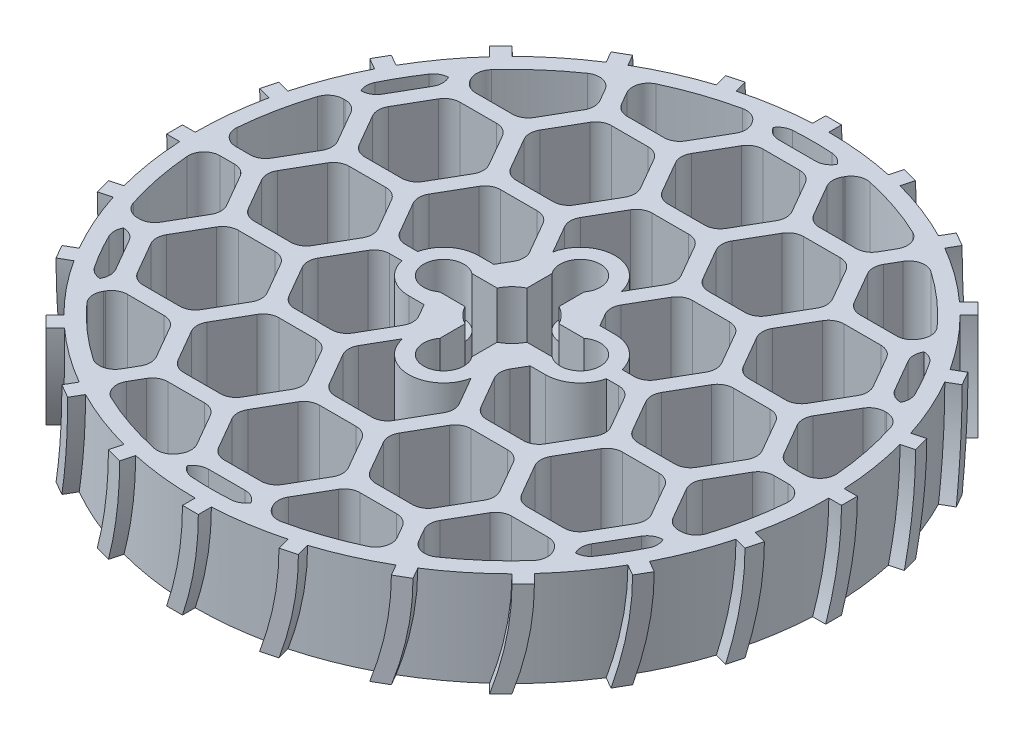
SolidWorks part; units mm, degrees
ref_plane "Front Plane" through (0, 0, 0) normal (0, 0, 1) x (1, 0, 0)
ref_plane "Top Plane" through (0, 0, 0) normal (0, 1, 0) x (1, 0, 0)
ref_plane "Right Plane" through (0, 0, 0) normal (1, 0, 0) x (0, 0, -1)
sketch "Sketch2" plane through (0, 0, 0) normal (0, 1, 0) x (1, 0, 0)
  line L0 (-17.7275, -5.0583) -> (-9.768, -5.0583)
  line L1 (-17.7275, 5.0583) -> (-9.768, 5.0583)
  line L2 (-21.548, 11) -> (-11, 11)
  line L3 (-21.548, -11) -> (-11, -11)
  line L4 (-21.548, 0) -> (0, 0) construction
  line L5 (11, 21.548) -> (11, 11)
  line L6 (-11, 21.548) -> (-11, 11)
  line L7 (5.0583, 17.7275) -> (5.0583, 9.768)
  line L8 (-5.0583, 17.7275) -> (-5.0583, 9.768)
  line L9 (21.548, -11) -> (11, -11)
  line L10 (21.548, 11) -> (11, 11)
  line L11 (17.7275, -5.0583) -> (9.768, -5.0583)
  line L12 (17.7275, 5.0583) -> (9.768, 5.0583)
  line L13 (-11, -21.548) -> (-11, -11)
  line L14 (11, -21.548) -> (11, -11)
  line L15 (-5.0583, -17.7275) -> (-5.0583, -9.768)
  line L16 (5.0583, -17.7275) -> (5.0583, -9.768)
  line L17 (0, 0) -> (-12.9904, 7.5) construction
  line L18 (-15.8771, -2.5) -> (-10.1036, -12.5)
  line L19 (-5.7735, -15) -> (5.7735, -15)
  line L20 (10.1036, -12.5) -> (15.8771, -2.5)
  line L21 (15.8771, 2.5) -> (10.1036, 12.5)
  line L22 (5.7735, 15) -> (-5.7735, 15)
  line L23 (-10.1036, 12.5) -> (-15.8771, 2.5)
  arc A0 (-21.548, 11) -> (-21.548, -11) centre (-21.548, 0) ccw
  arc A1 (-5.0583, 9.768) -> (-9.768, 5.0583) centre (0, 0) ccw
  circle A2 centre (-21.548, 0) radius 3.302
  circle A3 centre (-21.548, 0) radius 6.339
  arc A4 (-5.0583, 9.768) -> (-9.768, 5.0583) centre (0, 0) ccw
  arc A5 (11, 21.548) -> (-11, 21.548) centre (0, 21.548) ccw
  circle A6 centre (0, 21.548) radius 6.339
  circle A7 centre (0, 21.548) radius 3.302
  arc A8 (21.548, -11) -> (21.548, 11) centre (21.548, 0) ccw
  circle A9 centre (21.548, 0) radius 6.339
  circle A10 centre (21.548, 0) radius 3.302
  arc A11 (-11, -21.548) -> (11, -21.548) centre (0, -21.548) ccw
  circle A12 centre (0, -21.548) radius 6.339
  circle A13 centre (0, -21.548) radius 3.302
  arc A14 (9.768, 5.0583) -> (5.0583, 9.768) centre (0, 0) ccw
  arc A15 (5.0583, -9.768) -> (9.768, -5.0583) centre (0, 0) ccw
  arc A16 (-9.768, -5.0583) -> (-5.0583, -9.768) centre (0, 0) ccw
  circle A17 centre (0, 0) radius 100
  circle A18 centre (0, 0) radius 15 construction
  arc A19 (10.1036, 12.5) -> (5.7735, 15) centre (5.7735, 10) ccw
  arc A20 (15.8771, -2.5) -> (15.8771, 2.5) centre (11.547, 0) ccw
  arc A21 (10.1036, -12.5) -> (5.7735, -15) centre (5.7735, -10) cw
  arc A22 (-10.1036, -12.5) -> (-5.7735, -15) centre (-5.7735, -10) ccw
  arc A23 (-15.8771, -2.5) -> (-15.8771, 2.5) centre (-11.547, 0) cw
  arc A24 (-10.1036, 12.5) -> (-5.7735, 15) centre (-5.7735, 10) cw
  point P59 (0, 0)
  dimension "D1" = 6.604
  dimension "D2" = 12.678
  dimension "D3" = 11
  dimension "D8" = 22
  dimension "D10" = 200
  dimension "D12" = 5
  dimension "D4" = 21.548
  dimension "D5" = 7.9595
  dimension "D6" = 10.548
  dimension "D7" = 10.548
  dimension "D11" = 30
  dimension "D13" = 30
  dimension "D9" = 4
sketch "Sketch3" plane through (0, 0, 0) normal (0, 1, 0) x (1, 0, 0)
  line L0 (0, 0) -> (16.547, 0) construction
  line L1 (5.7735, 15) -> (-5.7735, 15)
  line L2 (-10.1036, 12.5) -> (-15.8771, 2.5)
  line L3 (-15.8771, -2.5) -> (-10.1036, -12.5)
  line L4 (-5.7735, -15) -> (5.7735, -15)
  line L5 (10.1036, -12.5) -> (15.8771, -2.5)
  line L6 (15.8771, 2.5) -> (10.1036, 12.5)
  line L7 (36.0844, 32.5) -> (24.5374, 32.5)
  line L8 (20.2073, 30) -> (14.4338, 20)
  line L9 (14.4338, 15) -> (20.2073, 5)
  line L10 (24.5374, 2.5) -> (36.0844, 2.5)
  line L11 (40.4145, 5) -> (46.188, 15)
  line L12 (46.188, 20) -> (40.4145, 30)
  line L13 (66.3953, 50) -> (54.8483, 50)
  line L14 (50.5181, 47.5) -> (44.7446, 37.5)
  line L15 (44.7446, 32.5) -> (50.5181, 22.5)
  line L16 (54.8483, 20) -> (66.3953, 20)
  line L17 (70.7254, 22.5) -> (76.4989, 32.5)
  line L18 (76.4989, 37.5) -> (70.7254, 47.5)
  line L19 (96.7062, 67.5) -> (85.1592, 67.5)
  line L20 (80.829, 65) -> (75.0555, 55)
  line L21 (75.0555, 50) -> (80.829, 40)
  line L22 (85.1592, 37.5) -> (96.7062, 37.5)
  line L23 (101.0363, 40) -> (106.8098, 50)
  line L24 (106.8098, 55) -> (101.0363, 65)
  line L25 (36.0844, 67.5) -> (24.5374, 67.5)
  line L26 (20.2073, 65) -> (14.4338, 55)
  line L27 (14.4338, 50) -> (20.2073, 40)
  line L28 (24.5374, 37.5) -> (36.0844, 37.5)
  line L29 (40.4145, 40) -> (46.188, 50)
  line L30 (46.188, 55) -> (40.4145, 65)
  line L31 (66.3953, 85) -> (54.8483, 85)
  line L32 (50.5181, 82.5) -> (44.7446, 72.5)
  line L33 (44.7446, 67.5) -> (50.5181, 57.5)
  line L34 (54.8483, 55) -> (66.3953, 55)
  line L35 (70.7254, 57.5) -> (76.4989, 67.5)
  line L36 (76.4989, 72.5) -> (70.7254, 82.5)
  line L37 (96.7062, 102.5) -> (85.1592, 102.5) [skipped]
  line L38 (80.829, 100) -> (75.0555, 90) [skipped]
  line L39 (75.0555, 85) -> (80.829, 75) [skipped]
  line L40 (85.1592, 72.5) -> (96.7062, 72.5) [skipped]
  line L41 (101.0363, 75) -> (106.8098, 85) [skipped]
  line L42 (106.8098, 90) -> (101.0363, 100) [skipped]
  line L43 (36.0844, 102.5) -> (24.5374, 102.5)
  line L44 (20.2073, 100) -> (14.4338, 90)
  line L45 (14.4338, 85) -> (20.2073, 75)
  line L46 (24.5374, 72.5) -> (36.0844, 72.5)
  line L47 (40.4145, 75) -> (46.188, 85)
  line L48 (46.188, 90) -> (40.4145, 100)
  line L49 (66.3953, 120) -> (54.8483, 120) [skipped]
  line L50 (50.5181, 117.5) -> (44.7446, 107.5) [skipped]
  line L51 (44.7446, 102.5) -> (50.5181, 92.5) [skipped]
  line L52 (54.8483, 90) -> (66.3953, 90) [skipped]
  line L53 (70.7254, 92.5) -> (76.4989, 102.5) [skipped]
  line L54 (76.4989, 107.5) -> (70.7254, 117.5) [skipped]
  line L55 (96.7062, 137.5) -> (85.1592, 137.5) [skipped]
  line L56 (80.829, 135) -> (75.0555, 125) [skipped]
  line L57 (75.0555, 120) -> (80.829, 110) [skipped]
  line L58 (85.1592, 107.5) -> (96.7062, 107.5) [skipped]
  line L59 (101.0363, 110) -> (106.8098, 120) [skipped]
  line L60 (106.8098, 125) -> (101.0363, 135) [skipped]
  line L61 (36.0844, 137.5) -> (24.5374, 137.5) [skipped]
  line L62 (20.2073, 135) -> (14.4338, 125) [skipped]
  line L63 (14.4338, 120) -> (20.2073, 110) [skipped]
  line L64 (24.5374, 107.5) -> (36.0844, 107.5) [skipped]
  line L65 (40.4145, 110) -> (46.188, 120) [skipped]
  line L66 (46.188, 125) -> (40.4145, 135) [skipped]
  line L67 (66.3953, 155) -> (54.8483, 155) [skipped]
  line L68 (50.5181, 152.5) -> (44.7446, 142.5) [skipped]
  line L69 (44.7446, 137.5) -> (50.5181, 127.5) [skipped]
  line L70 (54.8483, 125) -> (66.3953, 125) [skipped]
  line L71 (70.7254, 127.5) -> (76.4989, 137.5) [skipped]
  line L72 (76.4989, 142.5) -> (70.7254, 152.5) [skipped]
  line L73 (96.7062, 172.5) -> (85.1592, 172.5) [skipped]
  line L74 (80.829, 170) -> (75.0555, 160) [skipped]
  line L75 (75.0555, 155) -> (80.829, 145) [skipped]
  line L76 (85.1592, 142.5) -> (96.7062, 142.5) [skipped]
  line L77 (101.0363, 145) -> (106.8098, 155) [skipped]
  line L78 (106.8098, 160) -> (101.0363, 170) [skipped]
  line L79 (5.7735, 50) -> (-5.7735, 50) [skipped]
  line L80 (-10.1036, 47.5) -> (-15.8771, 37.5) [skipped]
  line L81 (-15.8771, 32.5) -> (-10.1036, 22.5) [skipped]
  line L82 (-5.7735, 20) -> (5.7735, 20) [skipped]
  line L83 (10.1036, 22.5) -> (15.8771, 32.5) [skipped]
  line L84 (15.8771, 37.5) -> (10.1036, 47.5) [skipped]
  line L85 (5.7735, 85) -> (-5.7735, 85) [skipped]
  line L86 (-10.1036, 82.5) -> (-15.8771, 72.5) [skipped]
  line L87 (-15.8771, 67.5) -> (-10.1036, 57.5) [skipped]
  line L88 (-5.7735, 55) -> (5.7735, 55) [skipped]
  line L89 (10.1036, 57.5) -> (15.8771, 67.5) [skipped]
  line L90 (15.8771, 72.5) -> (10.1036, 82.5) [skipped]
  line L91 (5.7735, 120) -> (-5.7735, 120) [skipped]
  line L92 (-10.1036, 117.5) -> (-15.8771, 107.5) [skipped]
  line L93 (-15.8771, 102.5) -> (-10.1036, 92.5) [skipped]
  line L94 (-5.7735, 90) -> (5.7735, 90) [skipped]
  line L95 (10.1036, 92.5) -> (15.8771, 102.5) [skipped]
  line L96 (15.8771, 107.5) -> (10.1036, 117.5) [skipped]
  line L97 (0, 0) -> (77.9423, 45) construction
  line L98 (106.8098, 20) -> (101.0363, 30)
  line L99 (96.7062, 32.5) -> (85.1592, 32.5)
  line L100 (80.829, 30) -> (75.0555, 20)
  line L101 (75.0555, 15) -> (80.829, 5)
  line L102 (85.1592, 2.5) -> (96.7062, 2.5)
  line L103 (101.0363, 5) -> (106.8098, 15)
  line L104 (106.8098, -15) -> (101.0363, -5)
  line L105 (96.7062, -2.5) -> (85.1592, -2.5)
  line L106 (80.829, -5) -> (75.0555, -15)
  line L107 (75.0555, -20) -> (80.829, -30)
  line L108 (85.1592, -32.5) -> (96.7062, -32.5)
  line L109 (101.0363, -30) -> (106.8098, -20)
  line L110 (106.8098, -50) -> (101.0363, -40)
  line L111 (96.7062, -37.5) -> (85.1592, -37.5)
  line L112 (80.829, -40) -> (75.0555, -50)
  line L113 (75.0555, -55) -> (80.829, -65)
  line L114 (85.1592, -67.5) -> (96.7062, -67.5)
  line L115 (101.0363, -65) -> (106.8098, -55)
  line L116 (76.4989, -32.5) -> (70.7254, -22.5)
  line L117 (66.3953, -20) -> (54.8483, -20)
  line L118 (50.5181, -22.5) -> (44.7446, -32.5)
  line L119 (44.7446, -37.5) -> (50.5181, -47.5)
  line L120 (54.8483, -50) -> (66.3953, -50)
  line L121 (70.7254, -47.5) -> (76.4989, -37.5)
  line L122 (76.4989, 2.5) -> (70.7254, 12.5)
  line L123 (66.3953, 15) -> (54.8483, 15)
  line L124 (50.5181, 12.5) -> (44.7446, 2.5)
  line L125 (44.7446, -2.5) -> (50.5181, -12.5)
  line L126 (54.8483, -15) -> (66.3953, -15)
  line L127 (70.7254, -12.5) -> (76.4989, -2.5)
  line L128 (46.188, -15) -> (40.4145, -5)
  line L129 (36.0844, -2.5) -> (24.5374, -2.5)
  line L130 (20.2073, -5) -> (14.4338, -15)
  line L131 (14.4338, -20) -> (20.2073, -30)
  line L132 (24.5374, -32.5) -> (36.0844, -32.5)
  line L133 (40.4145, -30) -> (46.188, -20)
  line L134 (70.7254, -82.5) -> (76.4989, -72.5)
  line L135 (76.4989, -67.5) -> (70.7254, -57.5)
  line L136 (66.3953, -55) -> (54.8483, -55)
  line L137 (50.5181, -57.5) -> (44.7446, -67.5)
  line L138 (44.7446, -72.5) -> (50.5181, -82.5)
  line L139 (54.8483, -85) -> (66.3953, -85)
  line L140 (40.4145, -100) -> (46.188, -90)
  line L141 (46.188, -85) -> (40.4145, -75)
  line L142 (36.0844, -72.5) -> (24.5374, -72.5)
  line L143 (20.2073, -75) -> (14.4338, -85)
  line L144 (14.4338, -90) -> (20.2073, -100)
  line L145 (24.5374, -102.5) -> (36.0844, -102.5)
  line L146 (10.1036, -117.5) -> (15.8771, -107.5)
  line L147 (15.8771, -102.5) -> (10.1036, -92.5)
  line L148 (5.7735, -90) -> (-5.7735, -90)
  line L149 (-10.1036, -92.5) -> (-15.8771, -102.5)
  line L150 (-15.8771, -107.5) -> (-10.1036, -117.5)
  line L151 (-5.7735, -120) -> (5.7735, -120)
  line L152 (10.1036, -82.5) -> (15.8771, -72.5)
  line L153 (15.8771, -67.5) -> (10.1036, -57.5)
  line L154 (5.7735, -55) -> (-5.7735, -55)
  line L155 (-10.1036, -57.5) -> (-15.8771, -67.5)
  line L156 (-15.8771, -72.5) -> (-10.1036, -82.5)
  line L157 (-5.7735, -85) -> (5.7735, -85)
  line L158 (40.4145, -65) -> (46.188, -55)
  line L159 (46.188, -50) -> (40.4145, -40)
  line L160 (36.0844, -37.5) -> (24.5374, -37.5)
  line L161 (20.2073, -40) -> (14.4338, -50)
  line L162 (14.4338, -55) -> (20.2073, -65)
  line L163 (24.5374, -67.5) -> (36.0844, -67.5)
  line L164 (10.1036, -47.5) -> (15.8771, -37.5)
  line L165 (15.8771, -32.5) -> (10.1036, -22.5)
  line L166 (5.7735, -20) -> (-5.7735, -20)
  line L167 (-10.1036, -22.5) -> (-15.8771, -32.5)
  line L168 (-15.8771, -37.5) -> (-10.1036, -47.5)
  line L169 (-5.7735, -50) -> (5.7735, -50)
  line L170 (-36.0844, -102.5) -> (-24.5374, -102.5)
  line L171 (-20.2073, -100) -> (-14.4338, -90)
  line L172 (-14.4338, -85) -> (-20.2073, -75)
  line L173 (-24.5374, -72.5) -> (-36.0844, -72.5)
  line L174 (-40.4145, -75) -> (-46.188, -85)
  line L175 (-46.188, -90) -> (-40.4145, -100)
  line L176 (-66.3953, -85) -> (-54.8483, -85)
  line L177 (-50.5181, -82.5) -> (-44.7446, -72.5)
  line L178 (-44.7446, -67.5) -> (-50.5181, -57.5)
  line L179 (-54.8483, -55) -> (-66.3953, -55)
  line L180 (-70.7254, -57.5) -> (-76.4989, -67.5)
  line L181 (-76.4989, -72.5) -> (-70.7254, -82.5)
  line L182 (-96.7062, -67.5) -> (-85.1592, -67.5)
  line L183 (-80.829, -65) -> (-75.0555, -55)
  line L184 (-75.0555, -50) -> (-80.829, -40)
  line L185 (-85.1592, -37.5) -> (-96.7062, -37.5)
  line L186 (-101.0363, -40) -> (-106.8098, -50)
  line L187 (-106.8098, -55) -> (-101.0363, -65)
  line L188 (-66.3953, -50) -> (-54.8483, -50)
  line L189 (-50.5181, -47.5) -> (-44.7446, -37.5)
  line L190 (-44.7446, -32.5) -> (-50.5181, -22.5)
  line L191 (-54.8483, -20) -> (-66.3953, -20)
  line L192 (-70.7254, -22.5) -> (-76.4989, -32.5)
  line L193 (-76.4989, -37.5) -> (-70.7254, -47.5)
  line L194 (-36.0844, -67.5) -> (-24.5374, -67.5)
  line L195 (-20.2073, -65) -> (-14.4338, -55)
  line L196 (-14.4338, -50) -> (-20.2073, -40)
  line L197 (-24.5374, -37.5) -> (-36.0844, -37.5)
  line L198 (-40.4145, -40) -> (-46.188, -50)
  line L199 (-46.188, -55) -> (-40.4145, -65)
  line L200 (-36.0844, -32.5) -> (-24.5374, -32.5)
  line L201 (-20.2073, -30) -> (-14.4338, -20)
  line L202 (-14.4338, -15) -> (-20.2073, -5)
  line L203 (-24.5374, -2.5) -> (-36.0844, -2.5)
  line L204 (-40.4145, -5) -> (-46.188, -15)
  line L205 (-46.188, -20) -> (-40.4145, -30)
  line L206 (-106.8098, -20) -> (-101.0363, -30)
  line L207 (-96.7062, -32.5) -> (-85.1592, -32.5)
  line L208 (-80.829, -30) -> (-75.0555, -20)
  line L209 (-75.0555, -15) -> (-80.829, -5)
  line L210 (-85.1592, -2.5) -> (-96.7062, -2.5)
  line L211 (-101.0363, -5) -> (-106.8098, -15)
  line L212 (-106.8098, 15) -> (-101.0363, 5)
  line L213 (-96.7062, 2.5) -> (-85.1592, 2.5)
  line L214 (-80.829, 5) -> (-75.0555, 15)
  line L215 (-75.0555, 20) -> (-80.829, 30)
  line L216 (-85.1592, 32.5) -> (-96.7062, 32.5)
  line L217 (-101.0363, 30) -> (-106.8098, 20)
  line L218 (-106.8098, 50) -> (-101.0363, 40)
  line L219 (-96.7062, 37.5) -> (-85.1592, 37.5)
  line L220 (-80.829, 40) -> (-75.0555, 50)
  line L221 (-75.0555, 55) -> (-80.829, 65)
  line L222 (-85.1592, 67.5) -> (-96.7062, 67.5)
  line L223 (-101.0363, 65) -> (-106.8098, 55)
  line L224 (-76.4989, 32.5) -> (-70.7254, 22.5)
  line L225 (-66.3953, 20) -> (-54.8483, 20)
  line L226 (-50.5181, 22.5) -> (-44.7446, 32.5)
  line L227 (-44.7446, 37.5) -> (-50.5181, 47.5)
  line L228 (-54.8483, 50) -> (-66.3953, 50)
  line L229 (-70.7254, 47.5) -> (-76.4989, 37.5)
  line L230 (-76.4989, -2.5) -> (-70.7254, -12.5)
  line L231 (-66.3953, -15) -> (-54.8483, -15)
  line L232 (-50.5181, -12.5) -> (-44.7446, -2.5)
  line L233 (-44.7446, 2.5) -> (-50.5181, 12.5)
  line L234 (-54.8483, 15) -> (-66.3953, 15)
  line L235 (-70.7254, 12.5) -> (-76.4989, 2.5)
  line L236 (-46.188, 15) -> (-40.4145, 5)
  line L237 (-36.0844, 2.5) -> (-24.5374, 2.5)
  line L238 (-20.2073, 5) -> (-14.4338, 15)
  line L239 (-14.4338, 20) -> (-20.2073, 30)
  line L240 (-24.5374, 32.5) -> (-36.0844, 32.5)
  line L241 (-40.4145, 30) -> (-46.188, 20)
  line L242 (-70.7254, 82.5) -> (-76.4989, 72.5)
  line L243 (-76.4989, 67.5) -> (-70.7254, 57.5)
  line L244 (-66.3953, 55) -> (-54.8483, 55)
  line L245 (-50.5181, 57.5) -> (-44.7446, 67.5)
  line L246 (-44.7446, 72.5) -> (-50.5181, 82.5)
  line L247 (-54.8483, 85) -> (-66.3953, 85)
  line L248 (-40.4145, 100) -> (-46.188, 90)
  line L249 (-46.188, 85) -> (-40.4145, 75)
  line L250 (-36.0844, 72.5) -> (-24.5374, 72.5)
  line L251 (-20.2073, 75) -> (-14.4338, 85)
  line L252 (-14.4338, 90) -> (-20.2073, 100)
  line L253 (-24.5374, 102.5) -> (-36.0844, 102.5)
  line L254 (-10.1036, 117.5) -> (-15.8771, 107.5)
  line L255 (-15.8771, 102.5) -> (-10.1036, 92.5)
  line L256 (-5.7735, 90) -> (5.7735, 90)
  line L257 (10.1036, 92.5) -> (15.8771, 102.5)
  line L258 (15.8771, 107.5) -> (10.1036, 117.5)
  line L259 (5.7735, 120) -> (-5.7735, 120)
  line L260 (-10.1036, 82.5) -> (-15.8771, 72.5)
  line L261 (-15.8771, 67.5) -> (-10.1036, 57.5)
  line L262 (-5.7735, 55) -> (5.7735, 55)
  line L263 (10.1036, 57.5) -> (15.8771, 67.5)
  line L264 (15.8771, 72.5) -> (10.1036, 82.5)
  line L265 (5.7735, 85) -> (-5.7735, 85)
  line L266 (-40.4145, 65) -> (-46.188, 55)
  line L267 (-46.188, 50) -> (-40.4145, 40)
  line L268 (-36.0844, 37.5) -> (-24.5374, 37.5)
  line L269 (-20.2073, 40) -> (-14.4338, 50)
  line L270 (-14.4338, 55) -> (-20.2073, 65)
  line L271 (-24.5374, 67.5) -> (-36.0844, 67.5)
  line L272 (-10.1036, 47.5) -> (-15.8771, 37.5)
  line L273 (-15.8771, 32.5) -> (-10.1036, 22.5)
  line L274 (-5.7735, 20) -> (5.7735, 20)
  line L275 (10.1036, 22.5) -> (15.8771, 32.5)
  line L276 (15.8771, 37.5) -> (10.1036, 47.5)
  line L277 (5.7735, 50) -> (-5.7735, 50)
  line L278 (0, 0) -> (0, 90) construction
  line L279 (0, 0) -> (-77.9423, 45) construction
  line L280 (-17.7275, -5.0583) -> (-9.768, -5.0583)
  line L281 (-17.7275, 5.0583) -> (-9.768, 5.0583)
  line L282 (-21.548, 11) -> (-11, 11)
  line L283 (-21.548, -11) -> (-11, -11)
  line L284 (0, 0) -> (-21.548, 0) construction
  line L285 (11, 21.548) -> (11, 11)
  line L286 (-11, 21.548) -> (-11, 11)
  line L287 (-5.0583, 17.7275) -> (-5.0583, 9.768)
  line L288 (5.0583, 17.7275) -> (5.0583, 9.768)
  line L289 (21.548, -11) -> (11, -11)
  line L290 (21.548, 11) -> (11, 11)
  line L291 (17.7275, 5.0583) -> (9.768, 5.0583)
  line L292 (17.7275, -5.0583) -> (9.768, -5.0583)
  line L293 (-11, -21.548) -> (-11, -11)
  line L294 (11, -21.548) -> (11, -11)
  line L295 (5.0583, -17.7275) -> (5.0583, -9.768)
  line L296 (-5.0583, -17.7275) -> (-5.0583, -9.768)
  circle A0 centre (0, 0) radius 15 construction
  arc A1 (10.1036, 12.5) -> (5.7735, 15) centre (5.7735, 10) ccw
  arc A2 (15.8771, 2.5) -> (15.8771, -2.5) centre (11.547, 0) cw
  arc A3 (5.7735, -15) -> (10.1036, -12.5) centre (5.7735, -10) ccw
  arc A4 (-5.7735, -15) -> (-10.1036, -12.5) centre (-5.7735, -10) cw
  arc A5 (-15.8771, -2.5) -> (-15.8771, 2.5) centre (-11.547, 0) cw
  arc A6 (-10.1036, 12.5) -> (-5.7735, 15) centre (-5.7735, 10) cw
  circle A7 centre (0, 0) radius 100
  arc A8 (20.2073, 30) -> (24.5374, 32.5) centre (24.5374, 27.5) cw
  arc A9 (40.4145, 30) -> (36.0844, 32.5) centre (36.0844, 27.5) ccw
  arc A10 (14.4338, 15) -> (14.4338, 20) centre (18.7639, 17.5) cw
  arc A11 (24.5374, 2.5) -> (20.2073, 5) centre (24.5374, 7.5) cw
  arc A12 (36.0844, 2.5) -> (40.4145, 5) centre (36.0844, 7.5) ccw
  arc A13 (46.188, 20) -> (46.188, 15) centre (41.8579, 17.5) cw
  arc A14 (50.5181, 47.5) -> (54.8483, 50) centre (54.8483, 45) cw
  arc A15 (70.7254, 47.5) -> (66.3953, 50) centre (66.3953, 45) ccw
  arc A16 (44.7446, 32.5) -> (44.7446, 37.5) centre (49.0748, 35) cw
  arc A17 (54.8483, 20) -> (50.5181, 22.5) centre (54.8483, 25) cw
  arc A18 (66.3953, 20) -> (70.7254, 22.5) centre (66.3953, 25) ccw
  arc A19 (76.4989, 37.5) -> (76.4989, 32.5) centre (72.1688, 35) cw
  arc A20 (80.829, 65) -> (85.1592, 67.5) centre (85.1592, 62.5) cw
  arc A21 (101.0363, 65) -> (96.7062, 67.5) centre (96.7062, 62.5) ccw
  arc A22 (75.0555, 50) -> (75.0555, 55) centre (79.3857, 52.5) cw
  arc A23 (85.1592, 37.5) -> (80.829, 40) centre (85.1592, 42.5) cw
  arc A24 (96.7062, 37.5) -> (101.0363, 40) centre (96.7062, 42.5) ccw
  arc A25 (106.8098, 55) -> (106.8098, 50) centre (102.4797, 52.5) cw
  arc A26 (20.2073, 65) -> (24.5374, 67.5) centre (24.5374, 62.5) cw
  arc A27 (40.4145, 65) -> (36.0844, 67.5) centre (36.0844, 62.5) ccw
  arc A28 (14.4338, 50) -> (14.4338, 55) centre (18.7639, 52.5) cw
  arc A29 (24.5374, 37.5) -> (20.2073, 40) centre (24.5374, 42.5) cw
  arc A30 (36.0844, 37.5) -> (40.4145, 40) centre (36.0844, 42.5) ccw
  arc A31 (46.188, 55) -> (46.188, 50) centre (41.8579, 52.5) cw
  arc A32 (50.5181, 82.5) -> (54.8483, 85) centre (54.8483, 80) cw
  arc A33 (70.7254, 82.5) -> (66.3953, 85) centre (66.3953, 80) ccw
  arc A34 (44.7446, 67.5) -> (44.7446, 72.5) centre (49.0748, 70) cw
  arc A35 (54.8483, 55) -> (50.5181, 57.5) centre (54.8483, 60) cw
  arc A36 (66.3953, 55) -> (70.7254, 57.5) centre (66.3953, 60) ccw
  arc A37 (76.4989, 72.5) -> (76.4989, 67.5) centre (72.1688, 70) cw
  arc A38 (80.829, 100) -> (85.1592, 102.5) centre (85.1592, 97.5) cw [skipped]
  arc A39 (101.0363, 100) -> (96.7062, 102.5) centre (96.7062, 97.5) ccw [skipped]
  arc A40 (75.0555, 85) -> (75.0555, 90) centre (79.3857, 87.5) cw [skipped]
  arc A41 (85.1592, 72.5) -> (80.829, 75) centre (85.1592, 77.5) cw [skipped]
  arc A42 (96.7062, 72.5) -> (101.0363, 75) centre (96.7062, 77.5) ccw [skipped]
  arc A43 (106.8098, 90) -> (106.8098, 85) centre (102.4797, 87.5) cw [skipped]
  arc A44 (20.2073, 100) -> (24.5374, 102.5) centre (24.5374, 97.5) cw
  arc A45 (40.4145, 100) -> (36.0844, 102.5) centre (36.0844, 97.5) ccw
  arc A46 (14.4338, 85) -> (14.4338, 90) centre (18.7639, 87.5) cw
  arc A47 (24.5374, 72.5) -> (20.2073, 75) centre (24.5374, 77.5) cw
  arc A48 (36.0844, 72.5) -> (40.4145, 75) centre (36.0844, 77.5) ccw
  arc A49 (46.188, 90) -> (46.188, 85) centre (41.8579, 87.5) cw
  arc A50 (50.5181, 117.5) -> (54.8483, 120) centre (54.8483, 115) cw [skipped]
  arc A51 (70.7254, 117.5) -> (66.3953, 120) centre (66.3953, 115) ccw [skipped]
  arc A52 (44.7446, 102.5) -> (44.7446, 107.5) centre (49.0748, 105) cw [skipped]
  arc A53 (54.8483, 90) -> (50.5181, 92.5) centre (54.8483, 95) cw [skipped]
  arc A54 (66.3953, 90) -> (70.7254, 92.5) centre (66.3953, 95) ccw [skipped]
  arc A55 (76.4989, 107.5) -> (76.4989, 102.5) centre (72.1688, 105) cw [skipped]
  arc A56 (80.829, 135) -> (85.1592, 137.5) centre (85.1592, 132.5) cw [skipped]
  arc A57 (101.0363, 135) -> (96.7062, 137.5) centre (96.7062, 132.5) ccw [skipped]
  arc A58 (75.0555, 120) -> (75.0555, 125) centre (79.3857, 122.5) cw [skipped]
  arc A59 (85.1592, 107.5) -> (80.829, 110) centre (85.1592, 112.5) cw [skipped]
  arc A60 (96.7062, 107.5) -> (101.0363, 110) centre (96.7062, 112.5) ccw [skipped]
  arc A61 (106.8098, 125) -> (106.8098, 120) centre (102.4797, 122.5) cw [skipped]
  arc A62 (20.2073, 135) -> (24.5374, 137.5) centre (24.5374, 132.5) cw [skipped]
  arc A63 (40.4145, 135) -> (36.0844, 137.5) centre (36.0844, 132.5) ccw [skipped]
  arc A64 (14.4338, 120) -> (14.4338, 125) centre (18.7639, 122.5) cw [skipped]
  arc A65 (24.5374, 107.5) -> (20.2073, 110) centre (24.5374, 112.5) cw [skipped]
  arc A66 (36.0844, 107.5) -> (40.4145, 110) centre (36.0844, 112.5) ccw [skipped]
  arc A67 (46.188, 125) -> (46.188, 120) centre (41.8579, 122.5) cw [skipped]
  arc A68 (50.5181, 152.5) -> (54.8483, 155) centre (54.8483, 150) cw [skipped]
  arc A69 (70.7254, 152.5) -> (66.3953, 155) centre (66.3953, 150) ccw [skipped]
  arc A70 (44.7446, 137.5) -> (44.7446, 142.5) centre (49.0748, 140) cw [skipped]
  arc A71 (54.8483, 125) -> (50.5181, 127.5) centre (54.8483, 130) cw [skipped]
  arc A72 (66.3953, 125) -> (70.7254, 127.5) centre (66.3953, 130) ccw [skipped]
  arc A73 (76.4989, 142.5) -> (76.4989, 137.5) centre (72.1688, 140) cw [skipped]
  arc A74 (80.829, 170) -> (85.1592, 172.5) centre (85.1592, 167.5) cw [skipped]
  arc A75 (101.0363, 170) -> (96.7062, 172.5) centre (96.7062, 167.5) ccw [skipped]
  arc A76 (75.0555, 155) -> (75.0555, 160) centre (79.3857, 157.5) cw [skipped]
  arc A77 (85.1592, 142.5) -> (80.829, 145) centre (85.1592, 147.5) cw [skipped]
  arc A78 (96.7062, 142.5) -> (101.0363, 145) centre (96.7062, 147.5) ccw [skipped]
  arc A79 (106.8098, 160) -> (106.8098, 155) centre (102.4797, 157.5) cw [skipped]
  arc A80 (-10.1036, 47.5) -> (-5.7735, 50) centre (-5.7735, 45) cw [skipped]
  arc A81 (10.1036, 47.5) -> (5.7735, 50) centre (5.7735, 45) ccw [skipped]
  arc A82 (-15.8771, 32.5) -> (-15.8771, 37.5) centre (-11.547, 35) cw [skipped]
  arc A83 (-5.7735, 20) -> (-10.1036, 22.5) centre (-5.7735, 25) cw [skipped]
  arc A84 (5.7735, 20) -> (10.1036, 22.5) centre (5.7735, 25) ccw [skipped]
  arc A85 (15.8771, 37.5) -> (15.8771, 32.5) centre (11.547, 35) cw [skipped]
  arc A86 (-10.1036, 82.5) -> (-5.7735, 85) centre (-5.7735, 80) cw [skipped]
  arc A87 (10.1036, 82.5) -> (5.7735, 85) centre (5.7735, 80) ccw [skipped]
  arc A88 (-15.8771, 67.5) -> (-15.8771, 72.5) centre (-11.547, 70) cw [skipped]
  arc A89 (-5.7735, 55) -> (-10.1036, 57.5) centre (-5.7735, 60) cw [skipped]
  arc A90 (5.7735, 55) -> (10.1036, 57.5) centre (5.7735, 60) ccw [skipped]
  arc A91 (15.8771, 72.5) -> (15.8771, 67.5) centre (11.547, 70) cw [skipped]
  arc A92 (-10.1036, 117.5) -> (-5.7735, 120) centre (-5.7735, 115) cw [skipped]
  arc A93 (10.1036, 117.5) -> (5.7735, 120) centre (5.7735, 115) ccw [skipped]
  arc A94 (-15.8771, 102.5) -> (-15.8771, 107.5) centre (-11.547, 105) cw [skipped]
  arc A95 (-5.7735, 90) -> (-10.1036, 92.5) centre (-5.7735, 95) cw [skipped]
  arc A96 (5.7735, 90) -> (10.1036, 92.5) centre (5.7735, 95) ccw [skipped]
  arc A97 (15.8771, 107.5) -> (15.8771, 102.5) centre (11.547, 105) cw [skipped]
  arc A98 (96.7062, 32.5) -> (101.0363, 30) centre (96.7062, 27.5) cw
  arc A99 (80.829, 30) -> (85.1592, 32.5) centre (85.1592, 27.5) cw
  arc A100 (75.0555, 15) -> (75.0555, 20) centre (79.3857, 17.5) cw
  arc A101 (80.829, 5) -> (85.1592, 2.5) centre (85.1592, 7.5) ccw
  arc A102 (101.0363, 5) -> (96.7062, 2.5) centre (96.7062, 7.5) cw
  arc A103 (106.8098, 15) -> (106.8098, 20) centre (102.4797, 17.5) ccw
  arc A104 (96.7062, -2.5) -> (101.0363, -5) centre (96.7062, -7.5) cw
  arc A105 (80.829, -5) -> (85.1592, -2.5) centre (85.1592, -7.5) cw
  arc A106 (75.0555, -20) -> (75.0555, -15) centre (79.3857, -17.5) cw
  arc A107 (80.829, -30) -> (85.1592, -32.5) centre (85.1592, -27.5) ccw
  arc A108 (101.0363, -30) -> (96.7062, -32.5) centre (96.7062, -27.5) cw
  arc A109 (106.8098, -20) -> (106.8098, -15) centre (102.4797, -17.5) ccw
  arc A110 (96.7062, -37.5) -> (101.0363, -40) centre (96.7062, -42.5) cw
  arc A111 (80.829, -40) -> (85.1592, -37.5) centre (85.1592, -42.5) cw
  arc A112 (75.0555, -55) -> (75.0555, -50) centre (79.3857, -52.5) cw
  arc A113 (80.829, -65) -> (85.1592, -67.5) centre (85.1592, -62.5) ccw
  arc A114 (101.0363, -65) -> (96.7062, -67.5) centre (96.7062, -62.5) cw
  arc A115 (106.8098, -55) -> (106.8098, -50) centre (102.4797, -52.5) ccw
  arc A116 (66.3953, -20) -> (70.7254, -22.5) centre (66.3953, -25) cw
  arc A117 (50.5181, -22.5) -> (54.8483, -20) centre (54.8483, -25) cw
  arc A118 (44.7446, -37.5) -> (44.7446, -32.5) centre (49.0748, -35) cw
  arc A119 (50.5181, -47.5) -> (54.8483, -50) centre (54.8483, -45) ccw
  arc A120 (70.7254, -47.5) -> (66.3953, -50) centre (66.3953, -45) cw
  arc A121 (76.4989, -37.5) -> (76.4989, -32.5) centre (72.1688, -35) ccw
  arc A122 (66.3953, 15) -> (70.7254, 12.5) centre (66.3953, 10) cw
  arc A123 (50.5181, 12.5) -> (54.8483, 15) centre (54.8483, 10) cw
  arc A124 (44.7446, -2.5) -> (44.7446, 2.5) centre (49.0748, 0) cw
  arc A125 (50.5181, -12.5) -> (54.8483, -15) centre (54.8483, -10) ccw
  arc A126 (70.7254, -12.5) -> (66.3953, -15) centre (66.3953, -10) cw
  arc A127 (76.4989, -2.5) -> (76.4989, 2.5) centre (72.1688, 0) ccw
  arc A128 (36.0844, -2.5) -> (40.4145, -5) centre (36.0844, -7.5) cw
  arc A129 (20.2073, -5) -> (24.5374, -2.5) centre (24.5374, -7.5) cw
  arc A130 (14.4338, -20) -> (14.4338, -15) centre (18.7639, -17.5) cw
  arc A131 (20.2073, -30) -> (24.5374, -32.5) centre (24.5374, -27.5) ccw
  arc A132 (40.4145, -30) -> (36.0844, -32.5) centre (36.0844, -27.5) cw
  arc A133 (46.188, -20) -> (46.188, -15) centre (41.8579, -17.5) ccw
  arc A134 (76.4989, -67.5) -> (76.4989, -72.5) centre (72.1688, -70) cw
  arc A135 (66.3953, -55) -> (70.7254, -57.5) centre (66.3953, -60) cw
  arc A136 (50.5181, -57.5) -> (54.8483, -55) centre (54.8483, -60) cw
  arc A137 (44.7446, -67.5) -> (44.7446, -72.5) centre (49.0748, -70) ccw
  arc A138 (54.8483, -85) -> (50.5181, -82.5) centre (54.8483, -80) cw
  arc A139 (66.3953, -85) -> (70.7254, -82.5) centre (66.3953, -80) ccw
  arc A140 (46.188, -85) -> (46.188, -90) centre (41.8579, -87.5) cw
  arc A141 (36.0844, -72.5) -> (40.4145, -75) centre (36.0844, -77.5) cw
  arc A142 (20.2073, -75) -> (24.5374, -72.5) centre (24.5374, -77.5) cw
  arc A143 (14.4338, -85) -> (14.4338, -90) centre (18.7639, -87.5) ccw
  arc A144 (24.5374, -102.5) -> (20.2073, -100) centre (24.5374, -97.5) cw
  arc A145 (36.0844, -102.5) -> (40.4145, -100) centre (36.0844, -97.5) ccw
  arc A146 (15.8771, -102.5) -> (15.8771, -107.5) centre (11.547, -105) cw
  arc A147 (5.7735, -90) -> (10.1036, -92.5) centre (5.7735, -95) cw
  arc A148 (-10.1036, -92.5) -> (-5.7735, -90) centre (-5.7735, -95) cw
  arc A149 (-15.8771, -102.5) -> (-15.8771, -107.5) centre (-11.547, -105) ccw
  arc A150 (-5.7735, -120) -> (-10.1036, -117.5) centre (-5.7735, -115) cw
  arc A151 (5.7735, -120) -> (10.1036, -117.5) centre (5.7735, -115) ccw
  arc A152 (15.8771, -67.5) -> (15.8771, -72.5) centre (11.547, -70) cw
  arc A153 (5.7735, -55) -> (10.1036, -57.5) centre (5.7735, -60) cw
  arc A154 (-10.1036, -57.5) -> (-5.7735, -55) centre (-5.7735, -60) cw
  arc A155 (-15.8771, -67.5) -> (-15.8771, -72.5) centre (-11.547, -70) ccw
  arc A156 (-5.7735, -85) -> (-10.1036, -82.5) centre (-5.7735, -80) cw
  arc A157 (5.7735, -85) -> (10.1036, -82.5) centre (5.7735, -80) ccw
  arc A158 (46.188, -50) -> (46.188, -55) centre (41.8579, -52.5) cw
  arc A159 (36.0844, -37.5) -> (40.4145, -40) centre (36.0844, -42.5) cw
  arc A160 (20.2073, -40) -> (24.5374, -37.5) centre (24.5374, -42.5) cw
  arc A161 (14.4338, -50) -> (14.4338, -55) centre (18.7639, -52.5) ccw
  arc A162 (24.5374, -67.5) -> (20.2073, -65) centre (24.5374, -62.5) cw
  arc A163 (36.0844, -67.5) -> (40.4145, -65) centre (36.0844, -62.5) ccw
  arc A164 (15.8771, -32.5) -> (15.8771, -37.5) centre (11.547, -35) cw
  arc A165 (5.7735, -20) -> (10.1036, -22.5) centre (5.7735, -25) cw
  arc A166 (-10.1036, -22.5) -> (-5.7735, -20) centre (-5.7735, -25) cw
  arc A167 (-15.8771, -32.5) -> (-15.8771, -37.5) centre (-11.547, -35) ccw
  arc A168 (-5.7735, -50) -> (-10.1036, -47.5) centre (-5.7735, -45) cw
  arc A169 (5.7735, -50) -> (10.1036, -47.5) centre (5.7735, -45) ccw
  arc A170 (-20.2073, -100) -> (-24.5374, -102.5) centre (-24.5374, -97.5) cw
  arc A171 (-14.4338, -85) -> (-14.4338, -90) centre (-18.7639, -87.5) cw
  arc A172 (-24.5374, -72.5) -> (-20.2073, -75) centre (-24.5374, -77.5) cw
  arc A173 (-36.0844, -72.5) -> (-40.4145, -75) centre (-36.0844, -77.5) ccw
  arc A174 (-46.188, -90) -> (-46.188, -85) centre (-41.8579, -87.5) cw
  arc A175 (-40.4145, -100) -> (-36.0844, -102.5) centre (-36.0844, -97.5) ccw
  arc A176 (-50.5181, -82.5) -> (-54.8483, -85) centre (-54.8483, -80) cw
  arc A177 (-44.7446, -67.5) -> (-44.7446, -72.5) centre (-49.0748, -70) cw
  arc A178 (-54.8483, -55) -> (-50.5181, -57.5) centre (-54.8483, -60) cw
  arc A179 (-66.3953, -55) -> (-70.7254, -57.5) centre (-66.3953, -60) ccw
  arc A180 (-76.4989, -72.5) -> (-76.4989, -67.5) centre (-72.1688, -70) cw
  arc A181 (-70.7254, -82.5) -> (-66.3953, -85) centre (-66.3953, -80) ccw
  arc A182 (-80.829, -65) -> (-85.1592, -67.5) centre (-85.1592, -62.5) cw
  arc A183 (-75.0555, -50) -> (-75.0555, -55) centre (-79.3857, -52.5) cw
  arc A184 (-85.1592, -37.5) -> (-80.829, -40) centre (-85.1592, -42.5) cw
  arc A185 (-96.7062, -37.5) -> (-101.0363, -40) centre (-96.7062, -42.5) ccw
  arc A186 (-106.8098, -55) -> (-106.8098, -50) centre (-102.4797, -52.5) cw
  arc A187 (-101.0363, -65) -> (-96.7062, -67.5) centre (-96.7062, -62.5) ccw
  arc A188 (-50.5181, -47.5) -> (-54.8483, -50) centre (-54.8483, -45) cw
  arc A189 (-44.7446, -32.5) -> (-44.7446, -37.5) centre (-49.0748, -35) cw
  arc A190 (-54.8483, -20) -> (-50.5181, -22.5) centre (-54.8483, -25) cw
  arc A191 (-66.3953, -20) -> (-70.7254, -22.5) centre (-66.3953, -25) ccw
  arc A192 (-76.4989, -37.5) -> (-76.4989, -32.5) centre (-72.1688, -35) cw
  arc A193 (-70.7254, -47.5) -> (-66.3953, -50) centre (-66.3953, -45) ccw
  arc A194 (-20.2073, -65) -> (-24.5374, -67.5) centre (-24.5374, -62.5) cw
  arc A195 (-14.4338, -50) -> (-14.4338, -55) centre (-18.7639, -52.5) cw
  arc A196 (-24.5374, -37.5) -> (-20.2073, -40) centre (-24.5374, -42.5) cw
  arc A197 (-36.0844, -37.5) -> (-40.4145, -40) centre (-36.0844, -42.5) ccw
  arc A198 (-46.188, -55) -> (-46.188, -50) centre (-41.8579, -52.5) cw
  arc A199 (-40.4145, -65) -> (-36.0844, -67.5) centre (-36.0844, -62.5) ccw
  arc A200 (-20.2073, -30) -> (-24.5374, -32.5) centre (-24.5374, -27.5) cw
  arc A201 (-14.4338, -15) -> (-14.4338, -20) centre (-18.7639, -17.5) cw
  arc A202 (-24.5374, -2.5) -> (-20.2073, -5) centre (-24.5374, -7.5) cw
  arc A203 (-36.0844, -2.5) -> (-40.4145, -5) centre (-36.0844, -7.5) ccw
  arc A204 (-46.188, -20) -> (-46.188, -15) centre (-41.8579, -17.5) cw
  arc A205 (-40.4145, -30) -> (-36.0844, -32.5) centre (-36.0844, -27.5) ccw
  arc A206 (-96.7062, -32.5) -> (-101.0363, -30) centre (-96.7062, -27.5) cw
  arc A207 (-80.829, -30) -> (-85.1592, -32.5) centre (-85.1592, -27.5) cw
  arc A208 (-75.0555, -15) -> (-75.0555, -20) centre (-79.3857, -17.5) cw
  arc A209 (-80.829, -5) -> (-85.1592, -2.5) centre (-85.1592, -7.5) ccw
  arc A210 (-101.0363, -5) -> (-96.7062, -2.5) centre (-96.7062, -7.5) cw
  arc A211 (-106.8098, -15) -> (-106.8098, -20) centre (-102.4797, -17.5) ccw
  arc A212 (-96.7062, 2.5) -> (-101.0363, 5) centre (-96.7062, 7.5) cw
  arc A213 (-80.829, 5) -> (-85.1592, 2.5) centre (-85.1592, 7.5) cw
  arc A214 (-75.0555, 20) -> (-75.0555, 15) centre (-79.3857, 17.5) cw
  arc A215 (-80.829, 30) -> (-85.1592, 32.5) centre (-85.1592, 27.5) ccw
  arc A216 (-101.0363, 30) -> (-96.7062, 32.5) centre (-96.7062, 27.5) cw
  arc A217 (-106.8098, 20) -> (-106.8098, 15) centre (-102.4797, 17.5) ccw
  arc A218 (-96.7062, 37.5) -> (-101.0363, 40) centre (-96.7062, 42.5) cw
  arc A219 (-80.829, 40) -> (-85.1592, 37.5) centre (-85.1592, 42.5) cw
  arc A220 (-75.0555, 55) -> (-75.0555, 50) centre (-79.3857, 52.5) cw
  arc A221 (-80.829, 65) -> (-85.1592, 67.5) centre (-85.1592, 62.5) ccw
  arc A222 (-101.0363, 65) -> (-96.7062, 67.5) centre (-96.7062, 62.5) cw
  arc A223 (-106.8098, 55) -> (-106.8098, 50) centre (-102.4797, 52.5) ccw
  arc A224 (-66.3953, 20) -> (-70.7254, 22.5) centre (-66.3953, 25) cw
  arc A225 (-50.5181, 22.5) -> (-54.8483, 20) centre (-54.8483, 25) cw
  arc A226 (-44.7446, 37.5) -> (-44.7446, 32.5) centre (-49.0748, 35) cw
  arc A227 (-50.5181, 47.5) -> (-54.8483, 50) centre (-54.8483, 45) ccw
  arc A228 (-70.7254, 47.5) -> (-66.3953, 50) centre (-66.3953, 45) cw
  arc A229 (-76.4989, 37.5) -> (-76.4989, 32.5) centre (-72.1688, 35) ccw
  arc A230 (-66.3953, -15) -> (-70.7254, -12.5) centre (-66.3953, -10) cw
  arc A231 (-50.5181, -12.5) -> (-54.8483, -15) centre (-54.8483, -10) cw
  arc A232 (-44.7446, 2.5) -> (-44.7446, -2.5) centre (-49.0748, 0) cw
  arc A233 (-50.5181, 12.5) -> (-54.8483, 15) centre (-54.8483, 10) ccw
  arc A234 (-70.7254, 12.5) -> (-66.3953, 15) centre (-66.3953, 10) cw
  arc A235 (-76.4989, 2.5) -> (-76.4989, -2.5) centre (-72.1688, 0) ccw
  arc A236 (-36.0844, 2.5) -> (-40.4145, 5) centre (-36.0844, 7.5) cw
  arc A237 (-20.2073, 5) -> (-24.5374, 2.5) centre (-24.5374, 7.5) cw
  arc A238 (-14.4338, 20) -> (-14.4338, 15) centre (-18.7639, 17.5) cw
  arc A239 (-20.2073, 30) -> (-24.5374, 32.5) centre (-24.5374, 27.5) ccw
  arc A240 (-40.4145, 30) -> (-36.0844, 32.5) centre (-36.0844, 27.5) cw
  arc A241 (-46.188, 20) -> (-46.188, 15) centre (-41.8579, 17.5) ccw
  arc A242 (-76.4989, 67.5) -> (-76.4989, 72.5) centre (-72.1688, 70) cw
  arc A243 (-66.3953, 55) -> (-70.7254, 57.5) centre (-66.3953, 60) cw
  arc A244 (-50.5181, 57.5) -> (-54.8483, 55) centre (-54.8483, 60) cw
  arc A245 (-44.7446, 67.5) -> (-44.7446, 72.5) centre (-49.0748, 70) ccw
  arc A246 (-54.8483, 85) -> (-50.5181, 82.5) centre (-54.8483, 80) cw
  arc A247 (-66.3953, 85) -> (-70.7254, 82.5) centre (-66.3953, 80) ccw
  arc A248 (-46.188, 85) -> (-46.188, 90) centre (-41.8579, 87.5) cw
  arc A249 (-36.0844, 72.5) -> (-40.4145, 75) centre (-36.0844, 77.5) cw
  arc A250 (-20.2073, 75) -> (-24.5374, 72.5) centre (-24.5374, 77.5) cw
  arc A251 (-14.4338, 85) -> (-14.4338, 90) centre (-18.7639, 87.5) ccw
  arc A252 (-24.5374, 102.5) -> (-20.2073, 100) centre (-24.5374, 97.5) cw
  arc A253 (-36.0844, 102.5) -> (-40.4145, 100) centre (-36.0844, 97.5) ccw
  arc A254 (-15.8771, 102.5) -> (-15.8771, 107.5) centre (-11.547, 105) cw
  arc A255 (-5.7735, 90) -> (-10.1036, 92.5) centre (-5.7735, 95) cw
  arc A256 (10.1036, 92.5) -> (5.7735, 90) centre (5.7735, 95) cw
  arc A257 (15.8771, 102.5) -> (15.8771, 107.5) centre (11.547, 105) ccw
  arc A258 (5.7735, 120) -> (10.1036, 117.5) centre (5.7735, 115) cw
  arc A259 (-5.7735, 120) -> (-10.1036, 117.5) centre (-5.7735, 115) ccw
  arc A260 (-15.8771, 67.5) -> (-15.8771, 72.5) centre (-11.547, 70) cw
  arc A261 (-5.7735, 55) -> (-10.1036, 57.5) centre (-5.7735, 60) cw
  arc A262 (10.1036, 57.5) -> (5.7735, 55) centre (5.7735, 60) cw
  arc A263 (15.8771, 67.5) -> (15.8771, 72.5) centre (11.547, 70) ccw
  arc A264 (5.7735, 85) -> (10.1036, 82.5) centre (5.7735, 80) cw
  arc A265 (-5.7735, 85) -> (-10.1036, 82.5) centre (-5.7735, 80) ccw
  arc A266 (-46.188, 50) -> (-46.188, 55) centre (-41.8579, 52.5) cw
  arc A267 (-36.0844, 37.5) -> (-40.4145, 40) centre (-36.0844, 42.5) cw
  arc A268 (-20.2073, 40) -> (-24.5374, 37.5) centre (-24.5374, 42.5) cw
  arc A269 (-14.4338, 50) -> (-14.4338, 55) centre (-18.7639, 52.5) ccw
  arc A270 (-24.5374, 67.5) -> (-20.2073, 65) centre (-24.5374, 62.5) cw
  arc A271 (-36.0844, 67.5) -> (-40.4145, 65) centre (-36.0844, 62.5) ccw
  arc A272 (-15.8771, 32.5) -> (-15.8771, 37.5) centre (-11.547, 35) cw
  arc A273 (-5.7735, 20) -> (-10.1036, 22.5) centre (-5.7735, 25) cw
  arc A274 (10.1036, 22.5) -> (5.7735, 20) centre (5.7735, 25) cw
  arc A275 (15.8771, 32.5) -> (15.8771, 37.5) centre (11.547, 35) ccw
  arc A276 (5.7735, 50) -> (10.1036, 47.5) centre (5.7735, 45) cw
  arc A277 (-5.7735, 50) -> (-10.1036, 47.5) centre (-5.7735, 45) ccw
  circle A278 centre (0, 0) radius 95
  arc A279 (-21.548, 11) -> (-21.548, -11) centre (-21.548, 0) ccw
  arc A280 (-9.5263, 5.5) -> (-9.768, 5.0583) centre (0, 0) ccw
  circle A281 centre (-21.548, 0) radius 3.302
  circle A282 centre (-21.548, 0) radius 6.339
  arc A283 (9.768, 5.0583) -> (9.768, -5.0583) centre (0, 0) ccw construction
  arc A284 (11, 21.548) -> (-11, 21.548) centre (0, 21.548) ccw
  circle A285 centre (0, 21.548) radius 6.339
  circle A286 centre (0, 21.548) radius 3.302
  arc A287 (21.548, -11) -> (21.548, 11) centre (21.548, 0) ccw
  circle A288 centre (21.548, 0) radius 6.339
  circle A289 centre (21.548, 0) radius 3.302
  arc A290 (-11, -21.548) -> (11, -21.548) centre (0, -21.548) ccw
  circle A291 centre (0, -21.548) radius 6.339
  circle A292 centre (0, -21.548) radius 3.302
  arc A293 (-9.768, -5.0583) -> (-5.0583, -9.768) centre (0, 0) ccw
  arc A294 (5.0583, -9.768) -> (9.768, -5.0583) centre (0, 0) ccw
  arc A295 (9.768, 5.0583) -> (5.0583, 9.768) centre (0, 0) ccw
  arc A296 (-5.0583, 9.768) -> (-9.768, 5.0583) centre (0, 0) ccw
  point P837 (0, 0)
  point P895 (0, 0)
  dimension "D3" = 5
  dimension "D4" = 200
  dimension "D11" = 5
  dimension "D12" = 11
  dimension "D14" = 6.604
  dimension "D15" = 12.678
  dimension "D19" = 22
  dimension "D1" = 30
  dimension "D2" = 0
  dimension "D7" = 5
  dimension "D8" = 5
  dimension "D9" = 5
  dimension "D13" = 21.548
  dimension "D16" = 7.9595
  dimension "D17" = 5.0583
  dimension "D18" = 5.0583
  dimension "D20" = 11
  dimension "D21" = 11
  dimension "D23" = 21.548
  dimension "D5" = 4
  dimension "D6" = 4
  dimension "D10" = 6
  dimension "D22" = 4
extrude "Boss-Extrude1" add sketch "Sketch3" along normal blind 30 contours L147 A278 L144 A143 L143 A142 L142 A141 L141 L138 A137 L137 A136 L136 A135 L135 L113 A112 L112 A111 L111 L108 A107 L107 A106 L106 A105 L105 L102 A101 L101 A100 L100 A99 L99 L22 A23 L21 A22 L20 L35 A36 L34 A35 L33 | A285 A274 L275 A284 L273 A273 | A285 A273 L273 A284 L286 L282 L238 A282 L281 L2 A6 L1 L287 | A288 L9 L290 L285 A284 L275 A274 A285 L288 L1 A1 L6 L291 | A282 L238 L282 A279 L237 | A282 L237 A279 L203 | A282 L203 A279 L283 L202 | A291 L296 L4 A4 L3 L280 A282 L202 L283 L293 A290 L167 A166 | A291 A166 L167 A290 L165 A165 | A291 A165 L165 A290 L294 L289 L130 A288 L292 L5 A3 L4 L295 | A288 L130 L289 A287 L129 | A288 L10 A287 L290 L9 | A288 L129 A287 L10 | A296 L287 L1 A6 L2 L281 A280 | A295 L291 L6 A1 L1 L288 | A294 L295 L4 A3 L5 L292 | A293 L280 L3 A4 L4 L296 | A278 L257 A7 L255 | A278 L44 A7 L257 | A278 L47 A49 A7 L44 | A278 L32 A32 A7 A49 L47 | A278 L35 A7 A32 L32 | A278 L20 A7 L35 | A278 L22 A7 L20 | A278 L99 A7 L22 | A278 L102 A102 A7 L99 | A278 L105 A104 A7 A102 L102 | A278 L108 A7 A104 L105 | A278 L111 A7 L108 | A278 L113 A7 L111 | A278 L135 A7 L113 | A278 L138 A138 A7 L135 | A278 L141 A140 A7 A138 L138 | A278 L144 A7 A140 L141 | A278 L147 A7 L144 | A278 L149 A7 L147 | A278 L171 A7 L149 | A278 L174 A174 A7 L171 | A278 L177 A176 A7 A174 L174 | A278 L180 A7 A176 L177 | A278 L183 A7 L180 | A278 L185 A7 L183 | A278 L207 A7 L185 | A278 L210 A210 A7 L207 | A278 L213 A212 A7 A210 L210 | A278 L216 A7 A212 L213 | A278 L219 A7 L216 | A278 L221 A7 L219 | A278 L243 A7 L221 | A278 L246 A246 A7 L243 | A278 L249 A248 A7 A246 L246 | A278 L252 A7 A248 L249 | A278 L255 A7 L252 region at (8.9743, 0, -9.8307) region at (5.4159, 0, -15.2364) region at (-8.9743, 0, -9.8307) region at (-5.4159, 0, -15.2364) region at (6.5394, 0, -20.7449) region at (24.9033, 0, -7.206) region at (16.0638, 0, 5.2947) region at (8.9743, 0, 9.8307) region at (30.0839, 0, 0) region at (24.9033, 0, 7.206) region at (-24.9033, 0, -7.206) region at (-30.0839, 0, 0) region at (-8.9743, 0, 9.8307) region at (-12.4566, 0, 8.8973) region at (-24.9033, 0, 7.206) region at (8.3023, 0, 20.9786) region at (84.2804, 0, -48.6593) region at (75.8084, 0, -61.2863) region at (73.2681, 0, -57.2596) region at (90.9797, 0, -35.0088) region at (63.1106, 0, -73.781) region at (95.4515, 0, -17.7648) region at (48.8193, 0, -84.5574) region at (97.6385, 0, 0) region at (32.341, 0, -91.5459) region at (15.1713, 0, -96.2952) region at (95.4515, 0, 17.7648) region at (0, 0, -97.3187) region at (90.9797, 0, 35.0088) region at (-15.1713, 0, -96.2952) region at (84.2804, 0, 48.6593) region at (-32.341, 0, -91.5459) region at (75.8084, 0, 61.2863) region at (-48.8193, 0, -84.5574) region at (63.1106, 0, 73.781) region at (-63.1106, 0, -73.781) region at (48.8193, 0, 84.5574) region at (-75.8084, 0, -61.2863) region at (32.341, 0, 91.5459) region at (-84.2804, 0, -48.6593) region at (15.1713, 0, 96.2952) region at (-90.9797, 0, -35.0088) region at (0, 0, 97.3187) region at (-95.4515, 0, -17.7648) region at (-15.1713, 0, 96.2952) region at (-97.6385, 0, 0) region at (-32.341, 0, 91.5459) region at (-95.4515, 0, 17.7648) region at (-48.8193, 0, 84.5574) region at (-90.9797, 0, 35.0088) region at (-63.1106, 0, 73.781) region at (-84.2804, 0, 48.6593) region at (-75.8084, 0, 61.2863)
extrude "Boss-Extrude2" add sketch "Sketch3<4>" along normal blind 15 contours A286 L274 A274 A285 A273 | A286 L274 A273 A285 A274 | A289 A11 L9 A288 L6 A2 L5 L130 A129 | A289 A11 L10 A288 L9 | A289 A129 L129 A288 L10 A11 | A289 A129 L130 A288 L129 | L6 A288 L5 A2 | L202 A282 L3 A5 L2 L238 A237 A281 A202 | L238 A282 L237 A237 A281 | L237 A282 L203 A202 A281 A237 | L203 A282 L202 A202 A281 | L3 A282 L2 A5 | A292 L166 A166 A291 A165 | A292 L166 A165 A291 A166 region at (0, 0, -17.7484) region at (5.9566, 0, -20.1528) region at (16.715, 0, -3.8899) region at (15.8617, 0, 0) region at (23.4226, 0, -4.3756) region at (26.0895, 0, 0) region at (-15.8617, 0, 0) region at (-15.9505, 0, -2.643) region at (23.4226, 0, 4.3756) region at (-23.4226, 0, -4.3756) region at (-26.0895, 0, 0) region at (-23.4226, 0, 4.3756) region at (0, 0, 17.7484) region at (6.1435, 0, 20.7936)
sketch "Sketch3<4>" plane through (0, 0, 0) normal (0, 1, 0) x (1, 0, 0) same geometry as "Sketch3"
ref_plane "Plane1" through (-100, 0, 0) normal (-1, 0, 0) x (0, 0, 1)
sketch "Sketch4" plane through (-100, 0, 0) normal (-1, 0, 0) x (0, 0, 1)
  line L0 (0, 30) -> (0, 0) construction
  line L1 (100, 30) -> (-100, 30) construction
  line L2 (0, 30) -> (0, 60) construction
  line L3 (0, 60) -> (-5, 60) construction
  line L4 (0, 0) -> (-5, 0)
  line L5 (-100, 0) -> (100, 0) construction
  line L6 (0, 30) -> (5, 30)
  spline S0 degree 2 poles (0, 0) (10, 30) (0, 60) knots 0 0 0 1 1 1
  spline S1 degree 2 poles (-5, 0) (5, 30) (-5, 60) knots 0 0 0 1 1 1
  dimension "D1" = 5
  dimension "D2" = 30
  dimension "D3" = 5
extrude "Boss-Extrude3" add sketch "Sketch4" along normal blind 4 and the other way blind 2 contours S1 L4 S0 L6 region at (-100, 15, 0.8333)
pattern_circular "CirPattern1" count 24 over 360 about axis through (0, 30, 0) along (0, -1, 0) of "Boss-Extrude3"
fillet "Fillet1" radius 5 36 edges at (89.2679, 15, -32.5) (-49.6486, 15, 80.9939) (-94.9671, 15, 2.5) (-87.2855, 15, 37.5) (-94.9671, 15, -2.5) (-89.2679, 15, 32.5) (-76.1187, 15, 56.8414) (-72.7798, 15, 61.0582) (11.1668, 15, 94.3414) (-11.1668, 15, 94.3414) (-16.4881, 15, 93.5582) (-45.3185, 15, 83.4939) (45.3185, 15, 83.4939) (16.4881, 15, 93.5582) (72.7798, 15, 61.0582) (49.6486, 15, 80.9939) (87.2855, 15, 37.5) (76.1187, 15, 56.8414) (94.9671, 15, 2.5) (89.2679, 15, 32.5) (49.6486, 15, -80.9939) (94.9671, 15, -2.5) (87.2855, 15, -37.5) (76.1187, 15, -56.8414) (72.7798, 15, -61.0582) (45.3185, 15, -83.4939) (16.4881, 15, -93.5582) (11.1668, 15, -94.3414) (-11.1668, 15, -94.3414) (-89.2679, 15, -32.5) (-87.2855, 15, -37.5) (-76.1187, 15, -56.8414) (-72.7798, 15, -61.0582) (-49.6486, 15, -80.9939) (-45.3185, 15, -83.4939) (-16.4881, 15, -93.5582)
